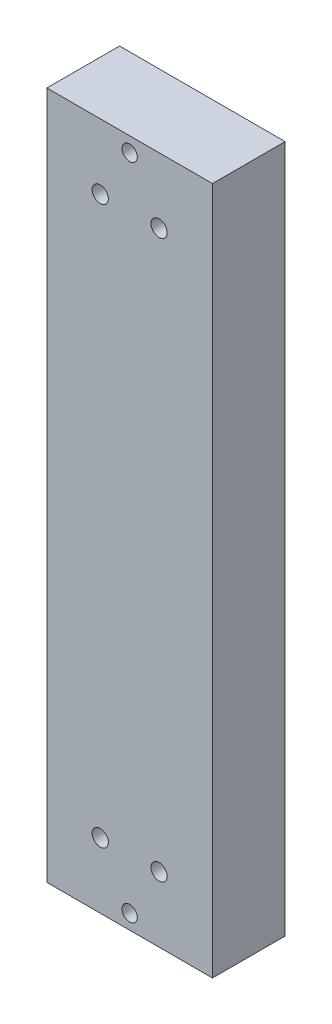
SolidWorks part; units mm, degrees
ref_plane "Front Plane" through (0, 0, 0) normal (0, 0, 1) x (1, 0, 0)
ref_plane "Top Plane" through (0, 0, 0) normal (0, 1, 0) x (1, 0, 0)
ref_plane "Right Plane" through (0, 0, 0) normal (1, 0, 0) x (0, 0, -1)
sketch "Sketch1" plane through (0, 0, 0) normal (0, 0, 1) x (1, 0, 0)
  line L1 (-6.5, -85.5) -> (6.5, -85.5)
  line L2 (-6.5, -85.5) -> (-6.5, 85.5)
  line L3 (-6.5, 85.5) -> (6.5, 85.5)
  line L4 (6.5, -85.5) -> (6.5, 85.5)
  line L5 (6.5, -84.5) -> (6.5, 84.5) construction
  line L6 (6.5, -85.5) -> (9.5, 85.5) construction
  line L7 (9.5, -85.5) -> (22.5, -85.5)
  line L8 (9.5, -85.5) -> (9.5, 85.5)
  line L9 (9.5, 85.5) -> (22.5, 85.5)
  line L10 (22.5, -85.5) -> (22.5, 85.5)
  line L11 (-14.5, -85.5) -> (30.5, -85.5)
  line L12 (-14.5, -93.5) -> (30.5, -93.5)
  line L13 (-14.5, -93.5) -> (-14.5, 93.5)
  line L14 (-14.5, 93.5) -> (30.5, 93.5)
  line L15 (30.5, -93.5) -> (30.5, 93.5)
  line L16 (-14.5, -93.5) -> (30.5, 93.5) construction
  line L17 (-14.5, 93.5) -> (30.5, -93.5) construction
  line L18 (-14.5, 85.5) -> (30.5, 85.5)
  line L19 (-12.5, -85.5) -> (-12.5, 85.5)
  line L20 (28.5, -85.5) -> (28.5, 85.5)
  line L21 (8, -93.5) -> (8, -85.5) construction
  line L22 (30.5, 0) -> (-14.5, 0) construction
  line L24 (-6.5, 84.5) -> (6.5, 84.5) construction
  line L25 (22.5, -84.5) -> (22.5, 84.5) construction
  line L26 (-6.5, -84.5) -> (-6.5, 84.5) construction
  line L27 (9.5, -84.5) -> (9.5, 84.5) construction
  line L28 (-6.5, -84.5) -> (6.5, -84.5) construction
  circle A0 centre (0, -75.75) radius 2.2
  circle A1 centre (16, -75.75) radius 2.2
  circle A2 centre (0, 75.75) radius 2.2
  circle A3 centre (16, 75.75) radius 2.2
  circle A4 centre (8, -89.5) radius 2.075
  circle A5 centre (8, 89.5) radius 2.075
  circle A6 centre (16, -75.75) radius 3 construction
  point P4 (0, 0)
  point P5 (16, -75.75)
  point P26 (8, 0)
  dimension "D3" = 4.15
  dimension "D8" = 4.4
  dimension "D1" = 8
  dimension "D2" = 8
  dimension "D4" = 2
  dimension "D5" = 2
  dimension "D6" = 1
  dimension "D7" = 1
extrude "Boss-Extrude1" add sketch "Sketch1" along normal blind 4.75 contours A2 | A3 | A0 | A1 | L13 L14 L15 L12 | A5 | A4 region at (0, -75.75, 0) region at (16, -75.75, 0) region at (0, 75.75, 0) region at (16, 75.75, 0)
extrude "Boss-Extrude2" add sketch "Sketch1<3>" against normal offset from surface (15 mm away) 2 contours L13 L18 L3 L9 L15 L14 A5 | L11 L19 L18 L13 | L12 L15 L11 L7 L1 L13 A4 | L20 L11 L15 L18 | L18 L4 L11 L8 region at (0, -85.9571, 0) region at (8, 0, 0) region at (-9.5, 85.9571, 0) region at (-13.5, 0, 0) region at (29.5, 0, 0) offset beyond the face yes
sketch "Sketch1<3>" plane through (0, 0, 0) normal (0, 0, 1) x (1, 0, 0) same geometry as "Sketch1"
equation "\"D5@Sketch1\"=\"D4@Sketch1\""
